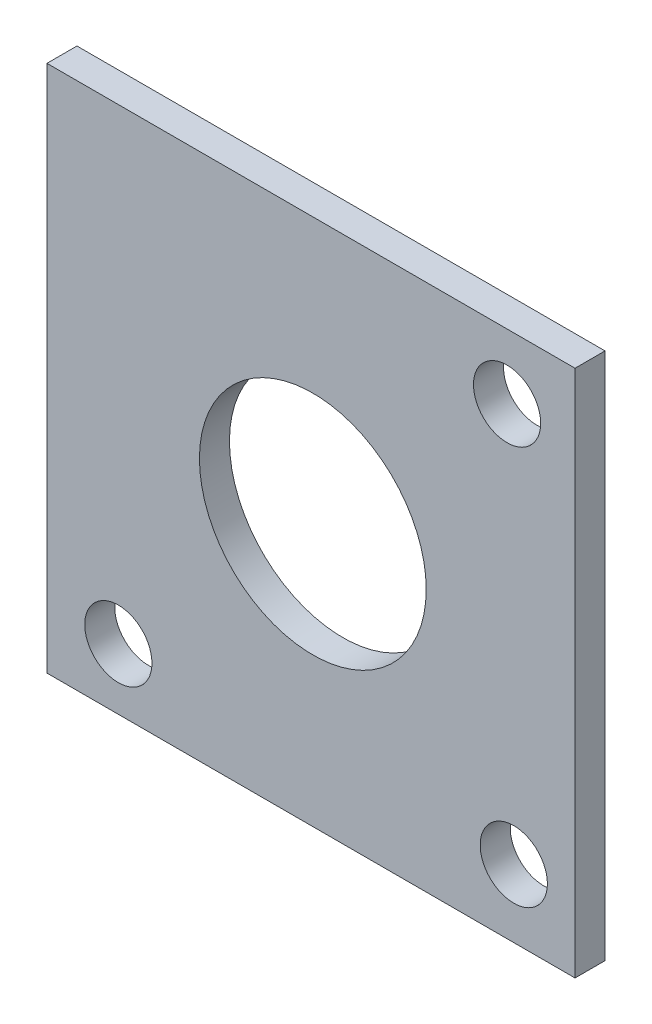
SolidWorks part; units mm, degrees
ref_plane "Front" through (0, 0, 0) normal (0, 0, 1) x (1, 0, 0)
ref_plane "Top" through (0, 0, 0) normal (0, 1, 0) x (1, 0, 0)
ref_plane "Right" through (0, 0, 0) normal (1, 0, 0) x (0, 0, -1)
sketch "Sketch2" plane through (0, 0, 0) normal (0, 0, 1) x (1, 0, 0)
  line L1 (-1.1, 1.1) -> (0, 1.1)
  line L2 (-1.1, 1.1) -> (-1.1, 0)
  line L3 (-1.1, 0) -> (0, 0)
  line L4 (0, 1.1) -> (0, 0)
  dimension "D1" = 1.1
  dimension "D2" = 1.1
extrude "Boss-Extrude1" add sketch "Sketch2" along normal blind 0.0625 contours L2 L3 L4 L1
sketch "Sketch3" plane through (0, 0, 0.0625) normal (0, 0, 1) x (1, 0, 0)
  circle A0 centre (-0.5462, 0.5459) radius 0.2362
  point P0 (0, 0)
  dimension "D1" = 0.4724
extrude "Cut-Extrude1" cut sketch "Sketch3" against normal through all
sketch "Sketch4" plane through (0, 0, 0.0625) normal (0, 0, 1) x (1, 0, 0)
  circle A0 centre (-0.5464, 0.5464) radius 0.5825
  circle A1 centre (-0.9653, 0.9508) radius 0.07 construction
  circle A2 centre (-0.1416, 0.9648) radius 0.07
  circle A3 centre (-0.1276, 0.1411) radius 0.07
  circle A4 centre (-0.9513, 0.1271) radius 0.07
  point P13 (-0.5464, 0.546)
  dimension "D1" = 1.1651
  dimension "D2" = 0.14
  dimension "D3" = 4
extrude "Cut-Extrude2" cut sketch "Sketch4" against normal through all contours A4 | A3 | A2
